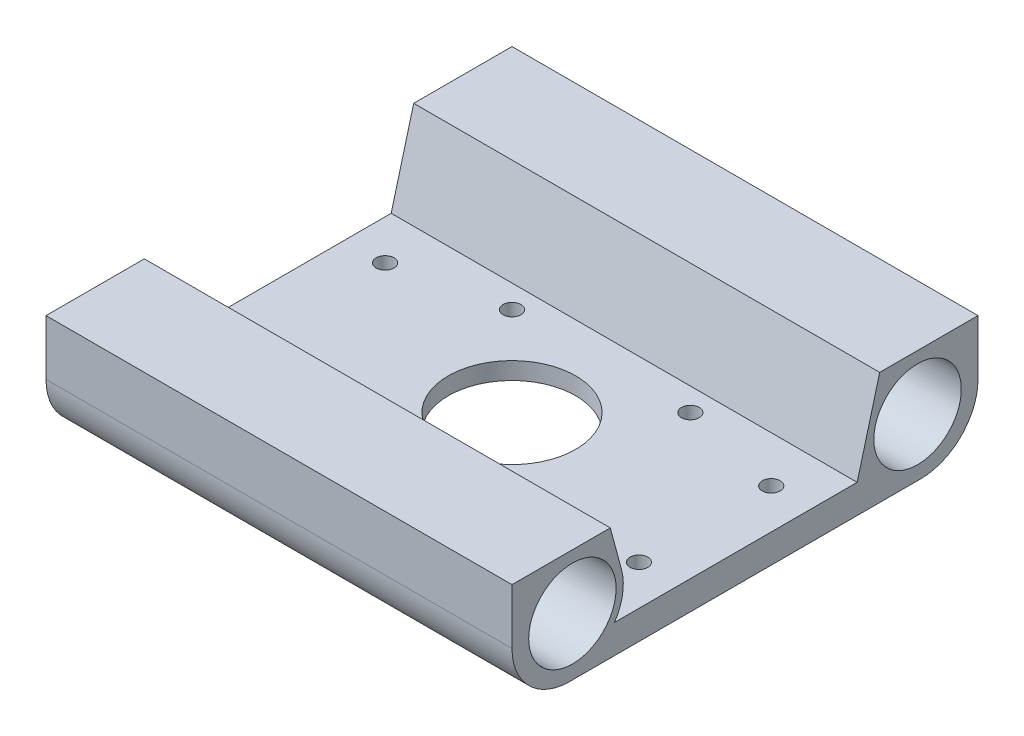
SolidWorks part; units mm, degrees
material "PLA (20%–30% infill + wall)"
ref_plane "Front Plane" through (0, 0, 0) normal (0, 0, 1) x (1, 0, 0)
ref_plane "Top Plane" through (0, 0, 0) normal (0, 1, 0) x (1, 0, 0)
ref_plane "Right Plane" through (0, 0, 0) normal (1, 0, 0) x (0, 0, -1)
sketch "Sketch1" plane through (0, 0, 0) normal (0, 1, 0) x (1, 0, 0)
  line L1 (-40.5, 40.5) -> (40.5, 40.5)
  line L2 (-40.5, 40.5) -> (-40.5, -40.5)
  line L3 (-40.5, -40.5) -> (40.5, -40.5)
  line L4 (40.5, 40.5) -> (40.5, -40.5)
  line L5 (-40.5, 40.5) -> (40.5, -40.5) construction
  line L6 (-40.5, -40.5) -> (40.5, 40.5) construction
  point P0 (0, 0)
  dimension "D1" = 81
  dimension "D2" = 81
extrude "Boss-Extrude1" add sketch "Sketch1" along normal blind 5
sketch "Sketch2" plane through (-40.5, 0, 0) normal (-1, 0, 0) x (0, 0, 1)
  line L0 (-30, 10) -> (-30, 5) construction
  line L1 (19.5, 5) -> (23.4121, 19.6)
  line L2 (-40.5, 5) -> (40.5, 5) construction
  line L3 (0, 0) -> (0, 23.7181) construction
  line L4 (-40.5, 5) -> (-40.5, 19.6)
  line L5 (-40.5, 19.6) -> (40.5, 19.6)
  line L6 (40.5, 5) -> (40.5, 19.6)
  line L7 (-40.5, 5) -> (40.5, 5)
  line L8 (-19.5, 5) -> (-23.4121, 19.6)
  circle A0 centre (-30, 10) radius 7.6
  circle A1 centre (-30, 10) radius 4 construction
  circle A2 centre (30, 10) radius 7.6
  circle A3 centre (30, 10) radius 4 construction
  point P14 (-30, 17.6)
  point P18 (0, 19.6)
  line M6 (40.5, 5) -> (-40.5, 5)
  dimension "D1" = 15.2
  dimension "D2" = 8
  dimension "D3" = 5
  dimension "D4" = 60
  dimension "D5" = 2
  dimension "D6" = 90
  dimension "D7" = 75
  dimension "D8" = 10.5
extrude "Boss-Extrude3" add sketch "Sketch2" against normal up to surface (81 mm away) contours A0 L7 L8 L5 L4 | A2 L6 L5 L1 M6 region at (-40.5, 12.2338, 21.7031) region at (-40.5, 5.2558, -21.8882) up to face at (40.5, 2.5, 0)
sketch "Sketch4" plane through (-40.5, 0, 0) normal (-1, 0, 0) x (0, 0, 1)
  circle A0 centre (-30, 10) radius 7.6
  circle A1 centre (30, 10) radius 7.6
  arc A2 (-24.2764, 5) -> (-35.7236, 5) centre (-30, 10) ccw construction
  arc A3 (35.7236, 5) -> (24.2764, 5) centre (30, 10) ccw construction
extrude "Cut-Extrude2" cut sketch "Sketch4" against normal through all
ref_plane "Plane1" through (0, 0, 0) normal (-1, 0, 0) x (0, 0, 1)
sketch "Sketch5" plane through (0, 5, 0) normal (0, 1, 0) x (1, 0, 0)
  circle A0 centre (0, 0) radius 11.075
  dimension "D1" = 22.15
extrude "Cut-Extrude3" cut sketch "Sketch5" against normal through all
sketch "Sketch6" plane through (0, 0, 0) normal (0, -1, 0) x (-1, 0, 0)
  line L0 (0, 0) -> (40.5, 0) construction
  line L1 (40.5, 40.5) -> (40.5, -40.5) construction
  line L2 (40.5, 0) -> (0, 0) construction
  line L3 (0, 0) -> (0, -40.5) construction
  line L4 (40.5, -40.5) -> (-40.5, -40.5) construction
  line L5 (0, 0) -> (-40.5, -40.5) construction
  circle A0 centre (-15.5, -15.5) radius 1.55
  circle A1 centre (15.5, -15.5) radius 1.55
  circle A2 centre (-15.5, 15.5) radius 1.55
  circle A3 centre (15.5, 15.5) radius 1.55
  dimension "D1" = 3.1
  dimension "D2" = 31
extrude "Cut-Extrude4" cut sketch "Sketch6" against normal through all
fillet "Fillet1" radius 10 2 edges at (0, 0, -40.5) (0, 0, 40.5)
sketch "Sketch7" plane through (0, 5, 0) normal (0, 1, 0) x (1, 0, 0)
  line L0 (-40.5, 0) -> (40.5, 0) construction
  line L1 (-40.5, 19.5) -> (-40.5, -19.5) construction
  line L2 (40.5, -19.5) -> (40.5, 19.5) construction
  line L3 (0, 10.78) -> (0, -10.78) construction
  circle A0 centre (-33.56, 11.5) radius 1.55
  circle A1 centre (-33.56, -11.5) radius 1.55
  circle A2 centre (33.56, 11.5) radius 1.55
  circle A3 centre (33.56, -11.5) radius 1.55
  dimension "D1" = 3.1
  dimension "D2" = 23
  dimension "D3" = 6.94
extrude "Cut-Extrude5" cut sketch "Sketch7" against normal blind 10
sketch "Sketch8" plane through (0, 0, 0) normal (0, -1, 0) x (-1, 0, 0)
  circle A0 centre (-33.56, -11.5) radius 1.55 construction
  circle A1 centre (33.56, -11.5) radius 1.55 construction
  circle A2 centre (33.56, 11.5) radius 1.55 construction
  circle A30 centre (33.56, -11.5) radius 3.55
  circle A36 centre (33.56, 11.5) radius 3.55
  circle A43 centre (-33.56, -11.5) radius 3.55
  circle A45 centre (-33.56, 11.5) radius 3.55
  circle A46 centre (-33.56, 11.5) radius 3.55
  dimension "D4" = 2
extrude "Cut-Extrude6" cut sketch "Sketch8" against normal blind 2.5
sketch "Sketch9" plane through (40.5, 0, 0) normal (1, 0, 0) x (0, 0, -1)
  line L0 (-19.5, 5) -> (-22.7, 5)
  line L1 (-22.7, 5) -> (-19.5, 5)
  line L3 (-21.4534, 12.2901) -> (-19.5, 5)
  arc A0 (-22.7, 5) -> (-21.4534, 12.2901) centre (-30, 10) ccw
extrude "Cut-Extrude8" cut sketch "Sketch9" against normal blind 18 contours A0 L0 region at (40.5, 6.8174, 20.9335)
sketch "Sketch10" plane through (0, 0, 0) normal (0, -1, 0) x (-1, 0, 0)
  line L1 (21.5, 21.5) -> (-21.5, 21.5)
  line L2 (21.5, 21.5) -> (21.5, -21.5)
  line L3 (21.5, -21.5) -> (-21.5, -21.5)
  line L4 (-21.5, 21.5) -> (-21.5, -21.5)
  line L5 (21.5, 21.5) -> (-21.5, -21.5) construction
  line L6 (21.5, -21.5) -> (-21.5, 21.5) construction
  point P0 (0, 0)
  dimension "D1" = 43
  dimension "D2" = 43
extrude "Cut-Extrude9" cut sketch "Sketch10" against normal blind 2
sketch "Sketch11" plane through (-40.5, 0, 0) normal (-1, 0, 0) x (0, 0, 1)
  line L0 (-6.45, 0) -> (6.45, 0)
  line L2 (-6.45, 0) -> (-6.45, 1)
  line L3 (-6.45, 1) -> (6.45, 1)
  line L4 (6.45, 0) -> (6.45, 1)
  line L5 (0, 0) -> (6.45, 1) construction
  line L6 (-6.45, 1) -> (0, 0) construction
  point P0 (0, 0)
  point P2 (0, 0)
  dimension "D1" = 12.9
  dimension "D2" = 1
extrude "Cut-Extrude10" cut sketch "Sketch11" against normal blind 6.5
sketch "Sketch12" plane through (-40.5, 0, 0) normal (-1, 0, 0) x (0, 0, 1)
  line L2 (-6.5, 0) -> (-6.5, -5.1)
  line L3 (-6.5, -5.1) -> (6.5, -5.1)
  line L4 (6.5, 0) -> (6.5, -5.1)
  line L5 (-7.5, -6.1) -> (7.5, -6.1)
  line L8 (-7.5, -6.1) -> (-10.9337, 0)
  line L9 (-30.5, 0) -> (-6.45, 0) construction
  line L10 (0, 0) -> (0, -10.1509) construction
  line L11 (7.5, -6.1) -> (10.9337, 0)
  line L12 (-10.9337, 0) -> (-6.5, 0)
  line L13 (6.5, 0) -> (10.9337, 0)
  line L14 (-7.5, 2) -> (-7.5, -6.1) construction
  line L15 (-6.5, 1) -> (6.5, 1) construction
  line L16 (-6.5, 1) -> (-6.5, -5.1) construction
  line L17 (-7.5, 2) -> (7.5, 2) construction
  line L18 (6.5, 1) -> (6.5, -5.1) construction
  line L19 (7.5, 2) -> (7.5, -6.1) construction
  line L20 (6.45, 1) -> (-6.45, 1) construction
  dimension "D1" = 6.1
  dimension "D3" = 7
  dimension "D4" = 13
  dimension "D2" = 1
extrude "Boss-Extrude4" add sketch "Sketch12" against normal blind 3
fillet "Fillet2" radius 1 2 edges at (-39, -6.1, -7.5) (-39, -6.1, 7.5)
fillet "Fillet3" radius 1 2 edges at (-37.5, 0, 8.7168) (-37.5, 0, -8.7168)
fillet "Fillet4" radius 1 2 edges at (-38.7823, 0, 10.9337) (-38.7823, 0, -10.9337)
ref_plane "Plane2" through (0, 0, 0) normal (-1, 0, 0) x (0, 0, 1)
sketch "Sketch13" plane through (0, 0, 0) normal (-1, 0, 0) x (0, 0, 1)
  circle A0 centre (30, 10) radius 7.6 construction
  circle A1 centre (-30, 10) radius 7.6 construction
  circle A2 centre (30, 10) radius 7.6
  circle A3 centre (-30, 10) radius 7.6
  circle A4 centre (-30, 10) radius 6
  circle A5 centre (30, 10) radius 6
  dimension "D1" = 12
  dimension "D2" = 12
extrude "Boss-Extrude5" add sketch "Sketch13" along normal mid plane 33
